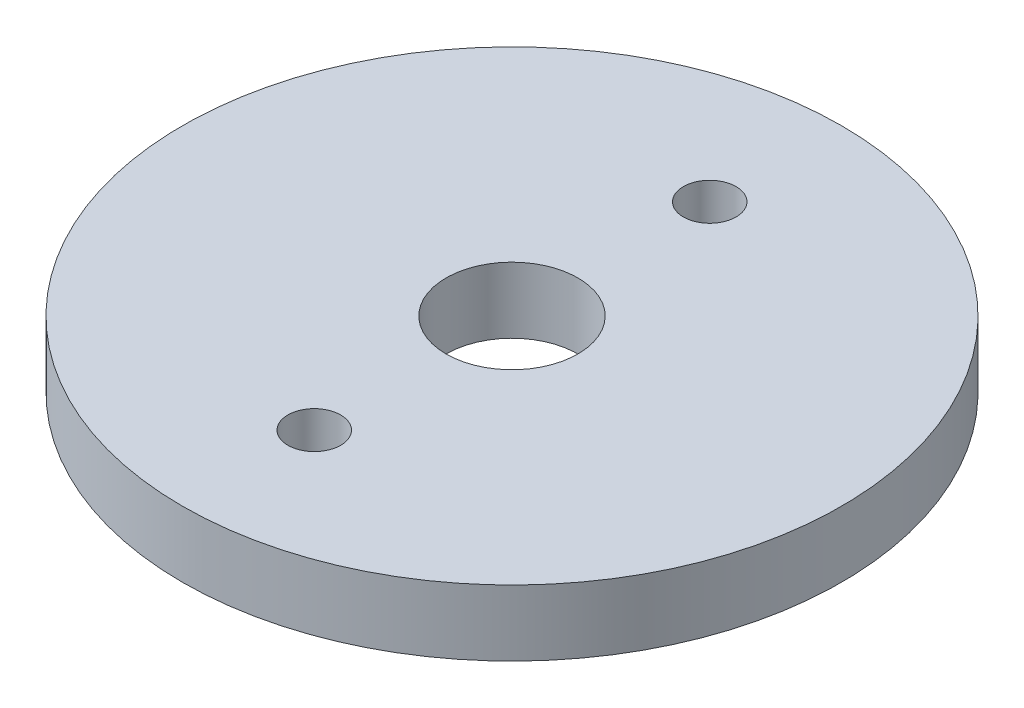
SolidWorks part; units mm, degrees
material "Acrylic (Medium-high impact)"
ref_plane "Front Plane" through (0, 0, 0) normal (0, 0, 1) x (1, 0, 0)
ref_plane "Top Plane" through (0, 0, 0) normal (0, 1, 0) x (1, 0, 0)
ref_plane "Right Plane" through (0, 0, 0) normal (1, 0, 0) x (0, 0, -1)
sketch "Sketch1" plane through (0, 0, 0) normal (0, 1, 0) x (1, 0, 0)
  circle A0 centre (0, 0) radius 20
  dimension "D1" = 40
sketch "Sketch2" plane through (0, 0, 0) normal (0, 1, 0) x (1, 0, 0)
  line L0 (-11.8283, 0) -> (13.8416, 0) construction
  circle A0 centre (0, 0) radius 4
  circle A1 centre (0, 12) radius 1.6
  circle A2 centre (0, -12) radius 1.6
  dimension "D1" = 8
  dimension "D2" = 3.2
  dimension "D3" = 12
extrude "Boss-Extrude1" add sketch "Sketch1" along normal blind 4
extrude "Cut-Extrude1" cut sketch "Sketch2" along normal up to next
